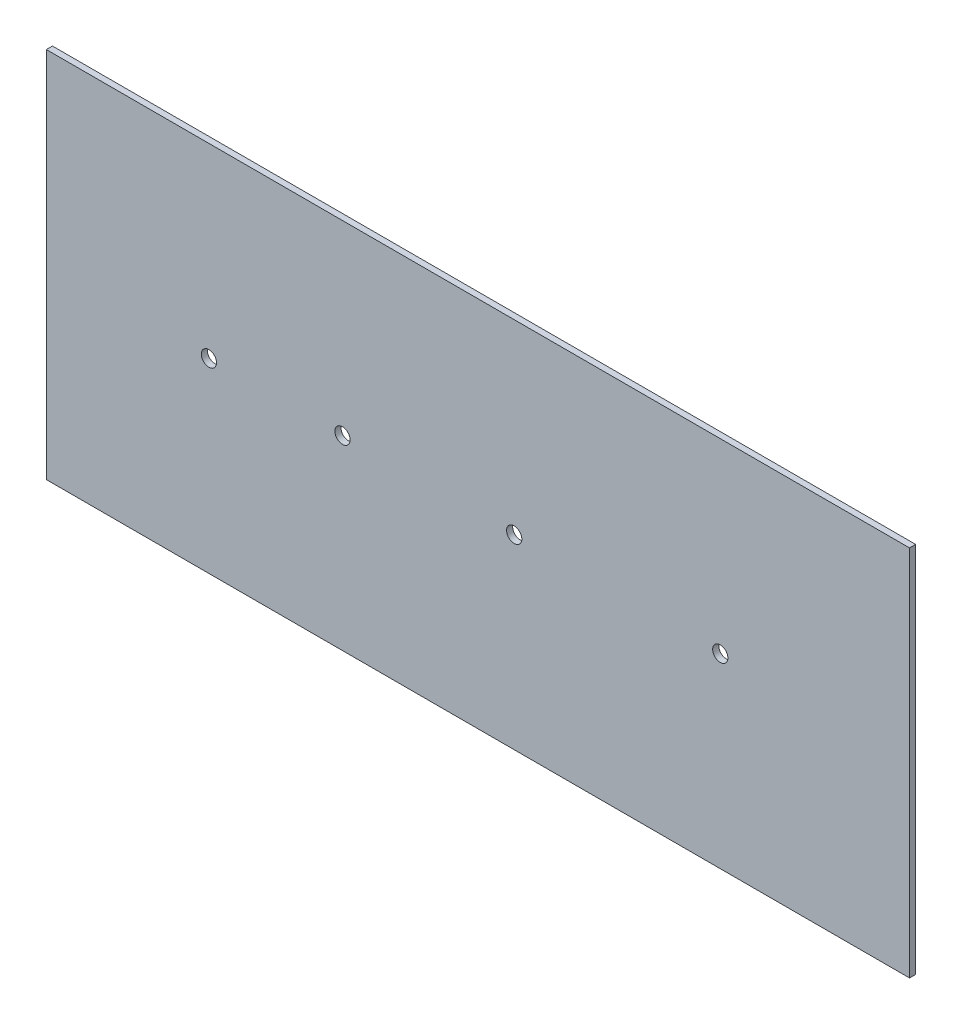
SolidWorks part; units mm, degrees
material "Сталь ШХ15 ГОСТ 801-78"
ref_plane "Plane1" through (0, 0, 0) normal (0, 0, 1) x (1, 0, 0)
ref_plane "Plane2" through (0, 0, 0) normal (0, 1, 0) x (1, 0, 0)
ref_plane "Plane3" through (0, 0, 0) normal (1, 0, 0) x (0, 0, -1)
sketch "Эскиз1" plane through (0, 0, 0) normal (0, 0, 1) x (1, 0, 0)
  line L0 (0, 61) -> (282.75, 61) construction
  line L1 (0, 0) -> (282.75, 0)
  line L2 (0, 0) -> (0, 122)
  line L3 (0, 122) -> (282.75, 122)
  line L4 (282.75, 0) -> (282.75, 122)
  circle A0 centre (22, 61) radius 11
  circle A1 centre (53.25, 61) radius 2.5
  circle A2 centre (97, 61) radius 2.5
  circle A3 centre (153.25, 61) radius 2.5
  circle A4 centre (220.75, 61) radius 2.5
  dimension "D3" = 22
  dimension "D4" = 22
  dimension "D5" = 5
  dimension "D6" = 31.25
  dimension "D9" = 62
  dimension "D1" = 122
  dimension "D2" = 67.5
  dimension "D7" = 43.75
  dimension "D8" = 56.25
extrude "Бобышка-Вытянуть1" add sketch "Эскиз1" along normal blind 2 contours L2 L0 A0 A1 A2 A3 A4 L4 L3 | L0 L2 L1 L4 A4 A3 A2 A1 A0 | A0 L0 | L0 A0 region at (142.732, 91.8564, 0) region at (142.732, 30.1436, 0) region at (22, 65.6685, 0) region at (22, 56.3315, 0)
